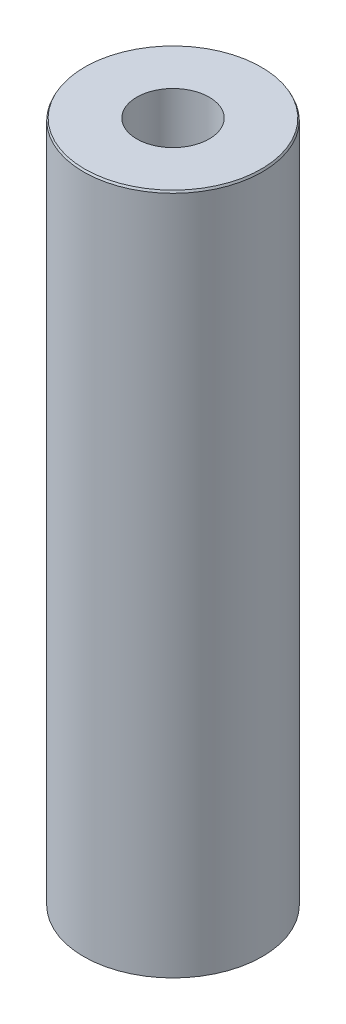
SolidWorks part; units mm, degrees
ref_plane "Front Plane" through (0, 0, 0) normal (0, 0, 1) x (1, 0, 0)
ref_plane "Top Plane" through (0, 0, 0) normal (0, 1, 0) x (1, 0, 0)
ref_plane "Right Plane" through (0, 0, 0) normal (1, 0, 0) x (0, 0, -1)
sketch "Sketch1" plane through (0, 0, 0) normal (0, 1, 0) x (1, 0, 0)
  circle A0 centre (0, 0) radius 37.5
  dimension "SHAFT_OD" = 75
extrude "Boss-Extrude1" add sketch "Sketch1" along normal blind 286.5325
sketch "Sketch2" plane through (0, 0, 0) normal (0, 1, 0) x (1, 0, 0)
  circle A0 centre (0, 0) radius 15.214
  dimension "BORE_D" = 30.4281
extrude "Cut-Extrude1" cut sketch "Sketch2" along normal through all
chamfer "Chamfer1" distance 0.8545 angle 26.181 2 edges at (0, 286.5325, 37.5) (0, 0, 37.5) first distance on face at (0, 286.5325, 37.5) first distance on face at (0, 0, 15.214)
